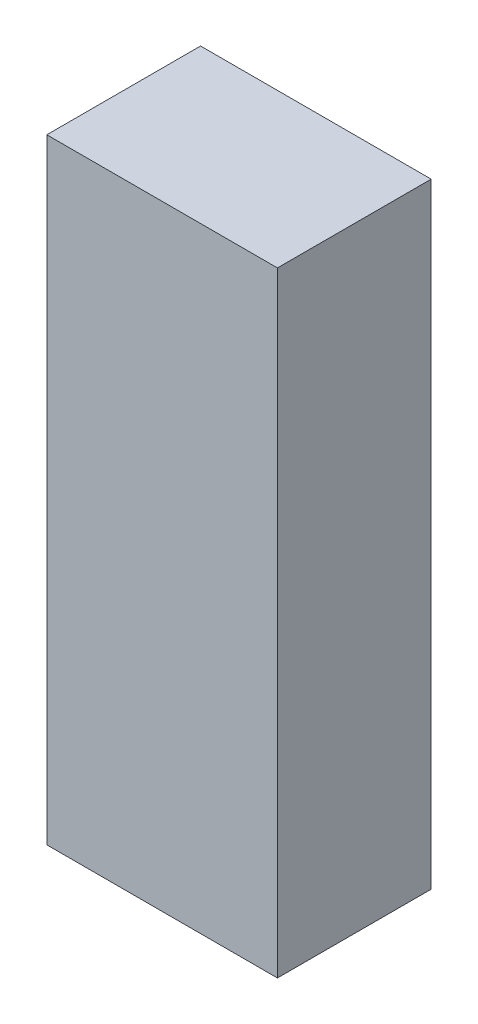
SolidWorks part; units mm, degrees
ref_plane "Front Plane" through (0, 0, 0) normal (0, 0, 1) x (1, 0, 0)
ref_plane "Top Plane" through (0, 0, 0) normal (0, 1, 0) x (1, 0, 0)
ref_plane "Right Plane" through (0, 0, 0) normal (1, 0, 0) x (0, 0, -1)
sketch "Sketch1" plane through (0, 0, 0) normal (0, 1, 0) x (1, 0, 0)
  line L1 (0, 0) -> (38.1, 0)
  line L2 (0, 0) -> (0, 25.4)
  line L3 (0, 25.4) -> (38.1, 25.4)
  line L4 (38.1, 0) -> (38.1, 25.4)
  dimension "D1" = 25.4
  dimension "D2" = 38.1
extrude "Boss-Extrude1" add sketch "Sketch1" along normal blind 101.6
